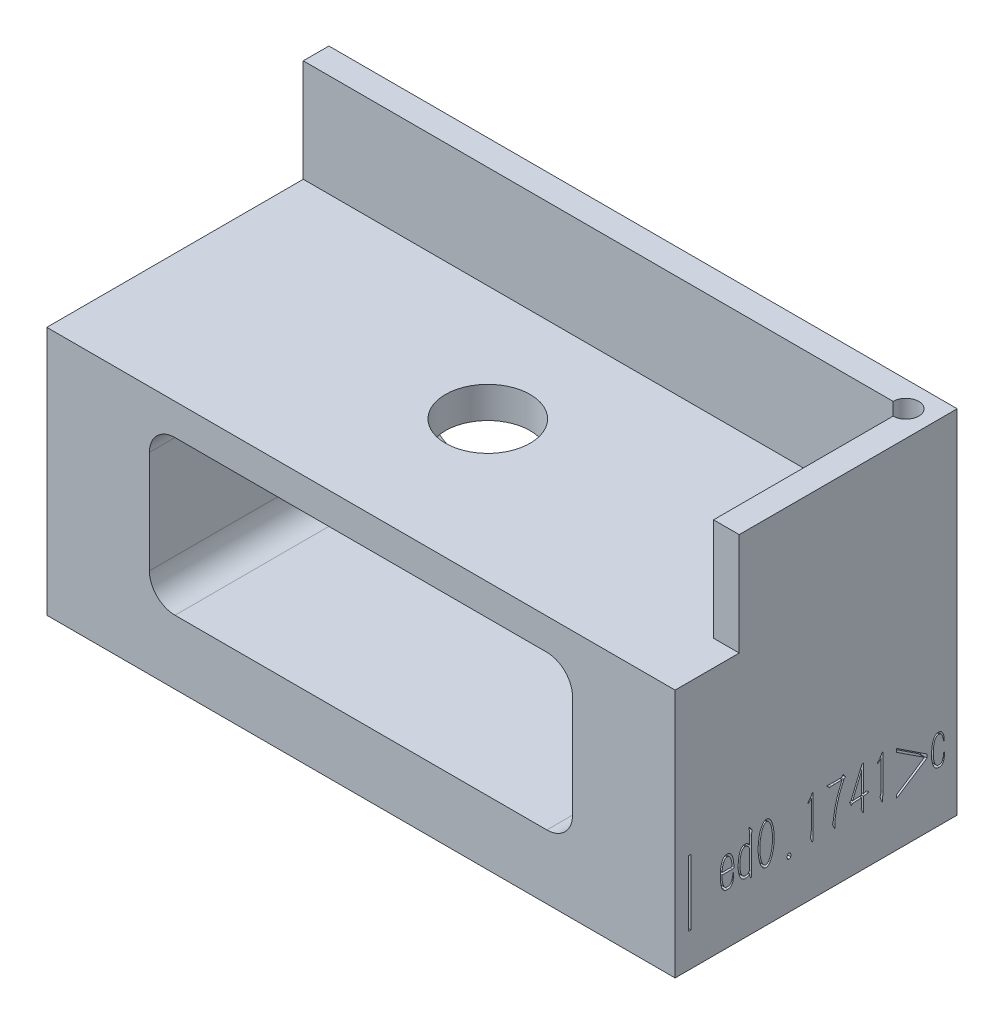
SolidWorks part; units mm, degrees
material "6061 合金"
ref_plane "前视基准面" through (0, 0, 0) normal (0, 0, 1) x (1, 0, 0)
ref_plane "上视基准面" through (0, 0, 0) normal (0, 1, 0) x (1, 0, 0)
ref_plane "右视基准面" through (0, 0, 0) normal (1, 0, 0) x (0, 0, -1)
sketch "草图1" plane through (0, 0, 0) normal (0, 1, 0) x (1, 0, 0)
  line L1 (-23.5, 9) -> (23.5, 9)
  line L2 (-23.5, 9) -> (-23.5, -9)
  line L3 (-23.5, -9) -> (23.5, -9)
  line L4 (23.5, 9) -> (23.5, -9)
  line L5 (-23.5, 9) -> (23.5, -9) construction
  line L6 (-23.5, -9) -> (23.5, 9) construction
  point P0 (0, 0)
  dimension "D1" = 47
  dimension "D2" = 18
extrude "凸台-拉伸1" add sketch "草图1" along normal blind 6
sketch "草图2" plane through (0, 6, 0) normal (0, 1, 0) x (1, 0, 0)
  line L1 (23.5, 9) -> (-23.5, 9) construction
  line L3 (23.5, 9) -> (-23.5, 9)
  line L12 (-23.5, -9) -> (23.5, -9) construction
  line L13 (-23.5, -9) -> (23.5, -9)
  line L19 (23.5, -9) -> (23.5, 9) construction
  line L20 (23.5, -9) -> (23.5, 9)
  line L21 (-23.5, -11) -> (25.5, -11)
  line L22 (25.5, -11) -> (25.5, 11)
  line L23 (25.5, 11) -> (-23.5, 11)
  line L24 (-23.5, -11) -> (-23.5, -9)
  line L25 (-23.5, 9) -> (-23.5, 11)
  dimension "D1" = 2
extrude "凸台-拉伸2" add sketch "草图2" along normal blind 8 and the other way through all
sketch "草图15" plane through (0, 0, 10) normal (0, 1, 0) x (1, 0, 0)
  line L4 (-23.5, -1) -> (25.5, -1)
  line L5 (-23.5, 21) -> (-23.5, -1)
  line L6 (25.5, 21) -> (-23.5, 21)
  line L7 (25.5, -1) -> (25.5, 21)
  line L12 (-23.5, -1) -> (25.5, -1)
  line L13 (-23.5, 21) -> (-23.5, -1)
  line L14 (25.5, 21) -> (-23.5, 21)
  line L15 (25.5, -1) -> (25.5, 21)
  dimension "D1" = 0
extrude "凸台-拉伸3" add sketch "草图15" against normal blind 5
sketch "草图12" plane through (-23.5, 0, 0) normal (-1, 0, 0) x (0, 0, 1)
  line L5 (9, 6) -> (11, 6)
  line L6 (9, 6) -> (9, 14)
  line L7 (9, 14) -> (11, 14)
  line L8 (11, 6) -> (11, 14)
extrude "切除-拉伸5" cut sketch "草图12" against normal offset from surface (37 mm away) 10 up to face at (23.5, 10, 0)
sketch "草图19" plane through (0, 0, 9) normal (0, 0, -1) x (-1, 0, 0)
  line L4 (-23.5, 6) -> (-13.5, 6)
  line L5 (-13.5, 6) -> (-13.5, 14)
  line L6 (-13.5, 14) -> (-23.5, 14)
  line L7 (-23.5, 14) -> (-23.5, 6)
  line L8 (-23.5, 6) -> (-13.5, 6)
  line L10 (-13.5, 14) -> (-23.5, 14)
  line L11 (-23.5, 14) -> (-23.5, 6)
  line L15 (-13.5, 6) -> (-13.5, 14)
  dimension "D1" = 0
extrude "凸台-拉伸4" add sketch "草图19" along normal blind 3
sketch "草图13" plane through (0, 14, 0) normal (0, 1, 0) x (1, 0, 0)
  circle A0 centre (23.5, 9) radius 1
extrude "切除-拉伸6" cut sketch "草图13" against normal up to surface (8 mm away) up to face at (4.5, 6, 2.6667)
sketch "草图5" plane through (0, -5, 0) normal (0, -1, 0) x (1, 0, 0)
  line L1 (-6.622, 9.4855) -> (18.378, 9.4855)
  line L2 (-6.622, 9.4855) -> (-6.622, -15.5145)
  line L3 (-6.622, -15.5145) -> (18.378, -15.5145)
  line L4 (18.378, 9.4855) -> (18.378, -15.5145)
  line L5 (-6.622, 9.4855) -> (18.378, -15.5145) construction
  line L6 (-6.622, -15.5145) -> (18.378, 9.4855) construction
  circle A0 centre (5.878, -3.0145) radius 2.3876 construction
  circle A1 centre (5.878, -3.0145) radius 2.3876 construction
  dimension "D1" = 25
  dimension "D2" = 25
extrude "切除-拉伸1" [suppressed] cut sketch "草图5" along normal up to surface (2.844 mm away)
sketch "草图3" plane through (0, -5, 0) normal (0, 1, 0) x (1, 0, 0)
  line L0 (-0.122, 9) -> (-0.122, 0.0145) construction
  line L1 (23.5, -6) -> (23.5, 8) construction
  line L3 (22.5, 9) -> (-23.5, 9) construction
  line L5 (-0.122, 0.0145) -> (23.5, 0.0145) construction
  circle A0 centre (-0.122, 0.0145) radius 1.3881
  circle A1 centre (-0.122, 0.0145) radius 2.5 construction
hole_wizard "打孔尺寸(%根据)内六角圆柱头螺钉的类型2" positions "3D草图1" profile "草图4" counterbore size "M6" standard "GB" end condition through all
sketch3d "3D草图1"
  point P0 (-0.122, -5, -0.0145)
sketch "草图4" plane through (-0.122, -5, -0.0145) normal (1, 0, 0) x (0, 0, -1)
  line L0 (0, 0) -> (0, 19)
  line L1 (0, 19) -> (3.3, 19)
  line L3 (3.3, 19) -> (3.3, 6.8)
  line L4 (3.3, 6.8) -> (5.5, 6.8)
  line L5 (5.5, 6.8) -> (5.5, 0)
  line L7 (5.5, 0) -> (0, 0)
  line L11 (0, -6.35) -> (0, 107.95) construction
  dimension "通孔孔直径" = 6.6
  dimension "通孔孔深度" = 19
  dimension "柱形沉头孔直径" = 11
  dimension "柱形沉头孔深度" = 6.8
sketch "草图6" [suppressed] plane through (0, -2.156, 0) normal (0, -1, 0) x (1, 0, 0)
  circle A2 centre (5.878, -3.0145) radius 5
  circle A4 centre (5.878, -3.0145) radius 2.3876 construction
hole_wizard "M4 螺纹孔4" [suppressed] positions "3D草图2" profile "草图20" tap size "M4" standard "GB"
sketch3d "3D草图2" [suppressed]
  point P0 (5.878, -2.156, -3.0145)
sketch "草图20" plane through (5.878, -2.156, -3.0145) normal (1, 0, 0) x (0, 0, -1)
  line L0 (0, 0) -> (0, 16.156)
  line L1 (0, 16.156) -> (1.65, 16.156)
  line L2 (1.65, 16.156) -> (1.65, 0)
  line L5 (1.65, 0) -> (0, 0)
  line L11 (0, -6.35) -> (0, 107.95) construction
  dimension "通孔螺纹孔钻头直径" = 3.3
  dimension "通孔螺纹孔钻头深度" = 16.156
cosmetic thread "孔螺蚊线6" [suppressed] parameters "D2"=4
sketch "草图17" [suppressed] plane through (18.378, 0, 0) normal (-1, 0, 0) x (0, 0, 1)
  line L4 (-11, -5) -> (9.4855, -5)
  line L5 (9.4855, -5) -> (9.4855, -2.156)
  line L6 (9.4855, -2.156) -> (-11, -2.156)
  line L7 (-11, -2.156) -> (-11, -5)
  line L10 (9.4855, -2.156) -> (-11, -2.156)
  line L14 (-11, -2.156) -> (-11, -5)
  line L15 (-11, -5) -> (9.4855, -5)
  line L16 (9.4855, -5) -> (9.4855, -2.156)
  dimension "D1" = 0
extrude "切除-拉伸8" [suppressed] cut sketch "草图17" against normal blind 1
sketch "草图18" [suppressed] plane through (0, -5, 0) normal (0, -1, 0) x (-1, 0, 0)
  line L0 (6.622, -9.4855) -> (6.622, 11) construction
  line L1 (-19.378, -9.4855) -> (6.622, -9.4855) construction
  circle A0 centre (6.622, -9.4855) radius 1
extrude "切除-拉伸9" [suppressed] cut sketch "草图18" against normal up to surface (2.844 mm away)
fillet "圆角1" [suppressed] radius 1
sketch "草图21" plane through (0, 0, 11) normal (0, 0, 1) x (1, 0, 0)
  text T0 "CS165MU/M"
extrude "切除-拉伸10" cut sketch "草图21" against normal blind 0.5
sketch "草图22" plane through (13.5, 0, 0) normal (-1, 0, 0) x (0, 0, 1)
  line L4 (11, 14) -> (6, 14)
  line L5 (6, 14) -> (6, 6)
  line L6 (6, 6) -> (11, 6)
  line L7 (11, 6) -> (11, 14)
  line L8 (11, 14) -> (6, 14)
  line L9 (6, 14) -> (6, 6)
  line L10 (6, 6) -> (11, 6)
  line L11 (11, 6) -> (11, 14)
  dimension "D1" = 0
extrude "切除-拉伸11" cut sketch "草图22" against normal through all
sketch "草图23" plane through (0, -5, 0) normal (0, -1, 0) x (1, 0, 0)
  line L4 (25.5, -11) -> (25.5, 11)
  line L5 (25.5, 11) -> (-23.5, 11)
  line L6 (-23.5, 11) -> (-23.5, -11)
  line L7 (-23.5, -11) -> (25.5, -11)
  line L8 (25.5, -11) -> (25.5, 11)
  line L9 (25.5, 11) -> (-23.5, 11)
  line L10 (-23.5, 11) -> (-23.5, -11)
  line L11 (-23.5, -11) -> (25.5, -11)
  dimension "D1" = 0
extrude "凸台-拉伸5" add sketch "草图23" along normal offset from surface (8.446 mm away) 3 offset beyond the face yes
sketch "草图24" plane through (0, -13.446, 0) normal (0, -1, 0) x (1, 0, 0)
  line L0 (-12.572, -3.0145) -> (12.328, -3.0145) construction
  line L1 (-12.622, 9.4855) -> (12.378, 9.4855)
  line L2 (-12.622, 9.4855) -> (-12.622, -15.5145)
  line L3 (-12.622, -15.5145) -> (12.378, -15.5145)
  line L4 (12.378, 9.4855) -> (12.378, -15.5145)
  line L5 (-12.622, 9.4855) -> (12.378, -15.5145) construction
  line L6 (-12.622, -15.5145) -> (12.378, 9.4855) construction
  point P0 (-0.122, -3.0145)
  dimension "D1" = 25
  dimension "D2" = 25
extrude "切除-拉伸12" cut sketch "草图24" against normal blind 3
sketch "草图26" plane through (0, -10.446, 0) normal (0, -1, 0) x (1, 0, 0)
  line L0 (-0.122, 9.4855) -> (-0.122, -3.0145) construction
  line L1 (12.378, 9.4855) -> (-12.622, 9.4855) construction
  line L3 (-0.122, -3.0145) -> (12.378, -3.0145) construction
  line L5 (-0.122, -9) -> (-0.122, -0.0145) construction
  circle A0 centre (-0.122, -3.0145) radius 0.8949
  dimension "D1" = 12.5
hole_wizard "M4 螺纹孔6" positions "3D草图5" profile "草图27" tap size "M4" standard "GB"
sketch3d "3D草图5"
  point P0 (-0.122, -10.446, -3.0145)
sketch "草图27" plane through (-0.122, -10.446, -3.0145) normal (1, 0, 0) x (0, 0, -1)
  line L0 (0, 0) -> (0, 5.9914)
  line L1 (0, 5.9914) -> (1.65, 5)
  line L2 (1.65, 5) -> (1.65, 0)
  line L5 (1.65, 0) -> (0, 0)
  line L10 (0, 5.9914) -> (-1.65, 5) construction
  line L11 (0, -6.35) -> (0, 107.95) construction
  dimension "螺纹孔钻头直径" = 3.3
  dimension "螺纹孔钻头深度" = 5
  dimension "导头角度" = 118
cosmetic thread "孔螺蚊线7" parameters "D1"=5, "D2"=4
sketch "草图28" plane through (0, 0, -11) normal (0, 0, -1) x (-1, 0, 0)
  line L0 (0.122, -10.446) -> (0.122, -8.446) construction
  line L1 (-0.7729, -10.446) -> (1.0169, -10.446) construction
  line L2 (0.122, -8.446) -> (15.5, -8.446) construction
  line L3 (23.5, -13.446) -> (23.5, 14) construction
  line L4 (15.5, -8.446) -> (-17.5, -8.446)
  line L5 (15.5, -8.446) -> (15.5, 3.554)
  line L6 (15.5, 3.554) -> (-17.5, 3.554)
  line L7 (-17.5, -8.446) -> (-17.5, 3.554)
  line L8 (-25.5, -13.446) -> (-25.5, 14) construction
  dimension "D1" = 2
  dimension "D2" = 12
  dimension "D3" = 8
  dimension "D4" = 8
extrude "切除-拉伸13" cut sketch "草图28" against normal through all
fillet "圆角2" radius 2 4 edges at (17.5, -8.446, 0) (-15.5, -8.446, 0) (-15.5, 3.554, 0) (17.5, 3.554, 0)
sketch "草图29" plane through (-12.5, 0, -11) normal (0, 0, 1) x (1, 0, 0)
  text T0 "CS165MU/M rail "
extrude "切除-拉伸14" cut sketch "草图29" along normal blind 0.5
sketch "草图31" plane through (12.378, 0, 0) normal (1, 0, 0) x (0, 0, -1)
  line L4 (11, -13.446) -> (11, -10.446)
  line L5 (11, -10.446) -> (-9.4855, -10.446)
  line L6 (-9.4855, -10.446) -> (-9.4855, -13.446)
  line L7 (-9.4855, -13.446) -> (11, -13.446)
  line L8 (11, -13.446) -> (11, -10.446)
  line L9 (11, -10.446) -> (-9.4855, -10.446)
  line L10 (-9.4855, -10.446) -> (-9.4855, -13.446)
  line L11 (-9.4855, -13.446) -> (11, -13.446)
  dimension "D1" = 0
extrude "切除-拉伸16" cut sketch "草图31" along normal blind 0.1741
sketch "草图30" plane through (0, -13.446, 0) normal (0, -1, 0) x (1, 0, 0)
  circle A0 centre (12.5521, 9.4855) radius 1
  circle A1 centre (-12.622, 9.4855) radius 1
extrude "切除-拉伸15" cut sketch "草图30" against normal up to surface (3 mm away) up to face at (-0.122, -10.446, -4.6645)
fillet "圆角3" [suppressed] radius 1
sketch "草图32" plane through (25.5, 0, 0) normal (1, 0, 0) x (0, 0, -1)
  text T0 "| ed0.1741>c "
extrude "切除-拉伸17" cut sketch "草图32" against normal blind 0.5
sketch "草图33" plane through (-23.5, 0, 0) normal (-1, 0, 0) x (0, 0, 1)
  text T0 "cen |"
extrude "切除-拉伸18" cut sketch "草图33" against normal blind 0.5
